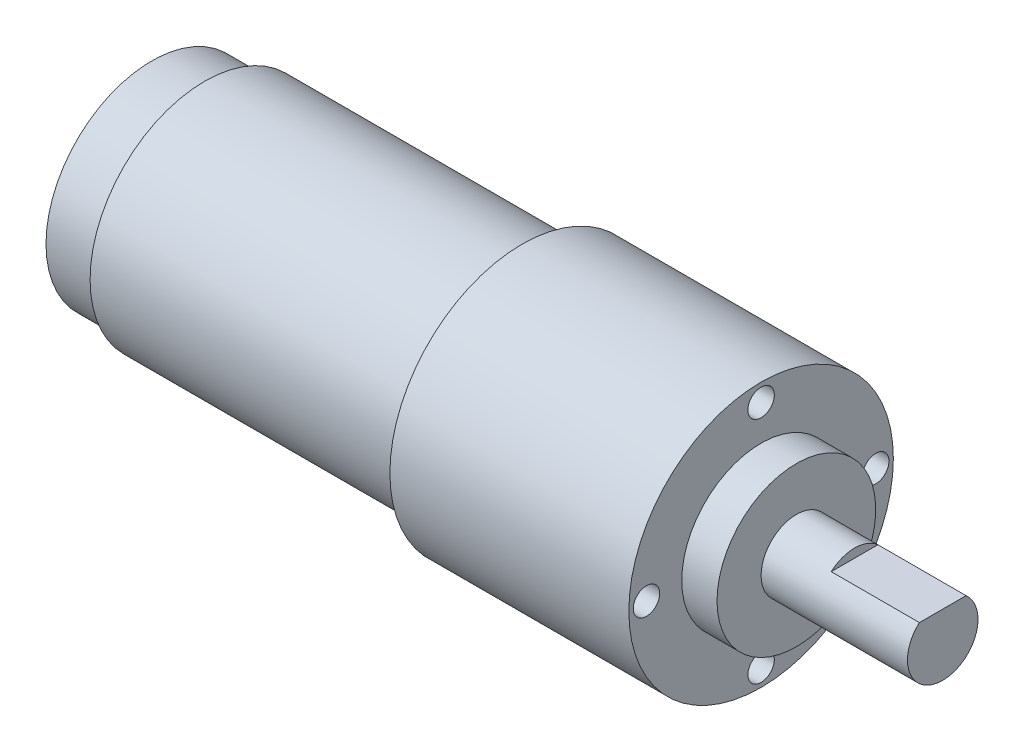
SolidWorks part; units mm, degrees
ref_plane "Plan de face" through (0, 0, 0) normal (0, 0, 1) x (1, 0, 0)
ref_plane "Plan de dessus" through (0, 0, 0) normal (0, 1, 0) x (1, 0, 0)
ref_plane "Plan de droite" through (0, 0, 0) normal (1, 0, 0) x (0, 0, -1)
ref_axis "Axe1" through (-5.325, 0, 0) along (1, 0, 0)
sketch "Esquisse1" plane through (0, 0, 0) normal (0, 0, 1) x (1, 0, 0)
  line L0 (0, 0) -> (93.7, 0)
  line L1 (93.7, 0) -> (93.7, 4)
  line L2 (93.7, 4) -> (77.1, 4)
  line L3 (77.1, 4) -> (77.1, 9)
  line L4 (77.1, 9) -> (73.1, 9)
  line L5 (73.1, 9) -> (73.1, 15)
  line L6 (73.1, 15) -> (46, 15)
  line L7 (46, 15) -> (46, 13)
  line L8 (46, 13) -> (10, 13)
  line L9 (10, 13) -> (10, 12)
  line L10 (10, 12) -> (4, 12)
  line L11 (4, 12) -> (4, 2)
  line L12 (4, 2) -> (0, 2)
  line L13 (0, 2) -> (0, 0)
  dimension "D1" = 27.1
  dimension "D2" = 4
  dimension "D3" = 20.6
  dimension "D4" = 13
  dimension "D5" = 15
  dimension "D6" = 9
  dimension "D7" = 12
  dimension "D8" = 2
  dimension "D9" = 42
  dimension "D10" = 6
  dimension "D11" = 4
  dimension "D12" = 4
  dimension "D13" = 93.7
revolve "MainRevolution" add sketch "Esquisse1" angle 360 about L0
sketch "Esquisse2" plane through (93.7, 0, 0) normal (1, 0, 0) x (0, 0, -1)
  line L1 (-2.6458, 3) -> (2.6458, 3)
  line L2 (-2.6458, 3) -> (-2.6458, 4)
  line L3 (-2.6458, 4) -> (2.6458, 4)
  line L4 (2.6458, 3) -> (2.6458, 4)
  circle A0 centre (0, 0) radius 4 construction
  circle A1 centre (0, 0) radius 4 construction
  dimension "D1" = 1
extrude "Enlèv. mat.-Extru.1" cut sketch "Esquisse2" against normal blind 10
sketch "Esquisse3" plane through (73.1, 0, 0) normal (1, 0, 0) x (0, 0, -1)
  line L0 (0, 55) -> (0, -55) construction
  circle A0 centre (0, 13) radius 1.5
  circle A1 centre (0, 0) radius 15 construction
  dimension "D1" = 3
  dimension "D2" = 13
extrude "FixHoles" cut sketch "Esquisse3" against normal blind 3
pattern_circular "RepeatFixHoles" count 4 every 90 about axis through (-5.325, 0, 0) along (1, 0, 0) of "FixHoles"
